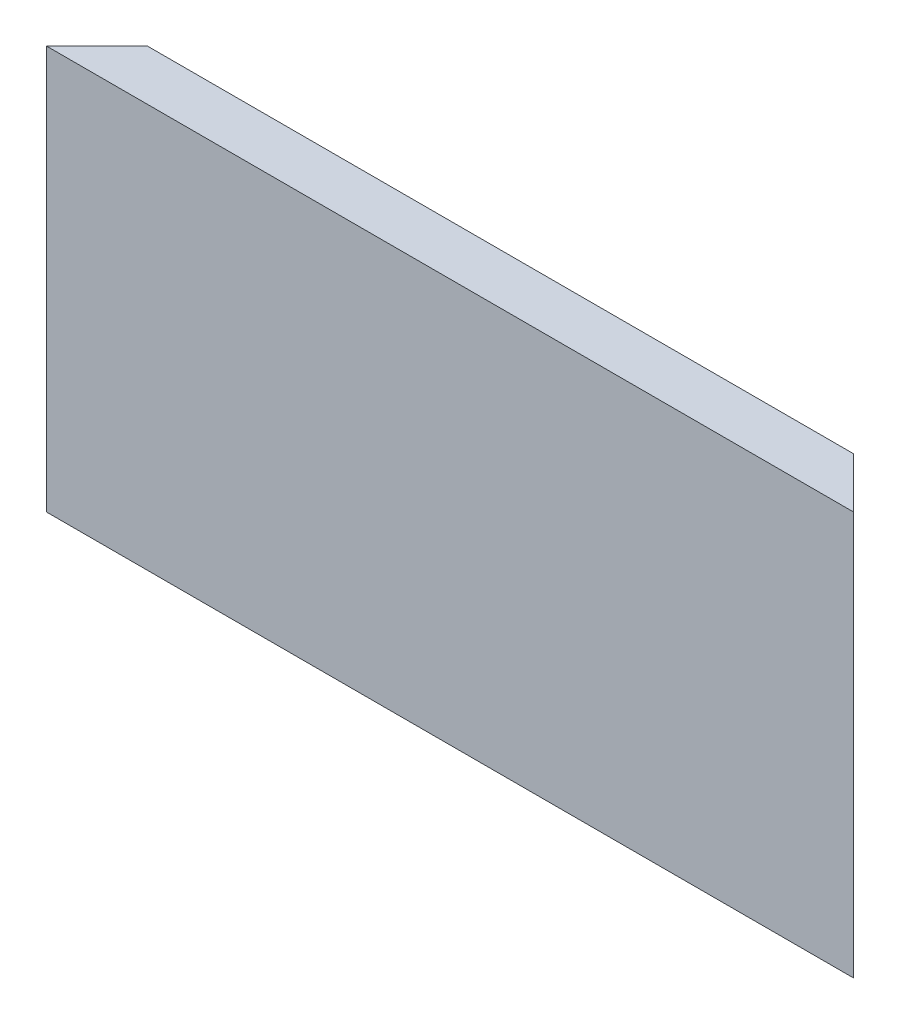
SolidWorks part; units mm, degrees
ref_plane "Front Plane" through (0, 0, 0) normal (0, 0, 1) x (1, 0, 0)
ref_plane "Top Plane" through (0, 0, 0) normal (0, 1, 0) x (1, 0, 0)
ref_plane "Right Plane" through (0, 0, 0) normal (1, 0, 0) x (0, 0, -1)
sketch "Sketch1" plane through (0, 0, 0) normal (1, 0, 0) x (0, 0, -1)
  line L0 (-2.5, -20) -> (2.5, -15)
  line L1 (-2.5, 20) -> (2.5, 20)
  line L2 (-2.5, 20) -> (-2.5, -20)
  line L4 (2.5, 20) -> (2.5, -15)
  line L5 (-2.5, 20) -> (2.5, -20) construction
  line L6 (-2.5, -20) -> (2.5, 20) construction
  point P0 (0, 0)
  dimension "D1" = 5
  dimension "D2" = 40
  dimension "D3" = 45
extrude "Boss-Extrude1" add sketch "Sketch1" along normal blind 80
sketch "Sketch2" plane through (0, 20, 0) normal (0, 1, 0) x (1, 0, 0)
  line L0 (80, 2.5) -> (0, 2.5) construction
  line L1 (80, 2.5) -> (75, 2.5)
  line L2 (0, -2.5) -> (5, 2.5)
  line L3 (80, -2.5) -> (0, -2.5) construction
  line L4 (80, -2.5) -> (75, 2.5)
  line L5 (80, 2.5) -> (80, -2.5) construction
  line L6 (80, 2.5) -> (80, -2.5)
  line L7 (0, 2.5) -> (0, -2.5) construction
  line L8 (0, 2.5) -> (0, -2.5)
  line L9 (5, 2.5) -> (0, 2.5)
  dimension "D1" = 45
  dimension "D2" = 45
extrude "Cut-Extrude1" cut sketch "Sketch2" against normal blind 80
